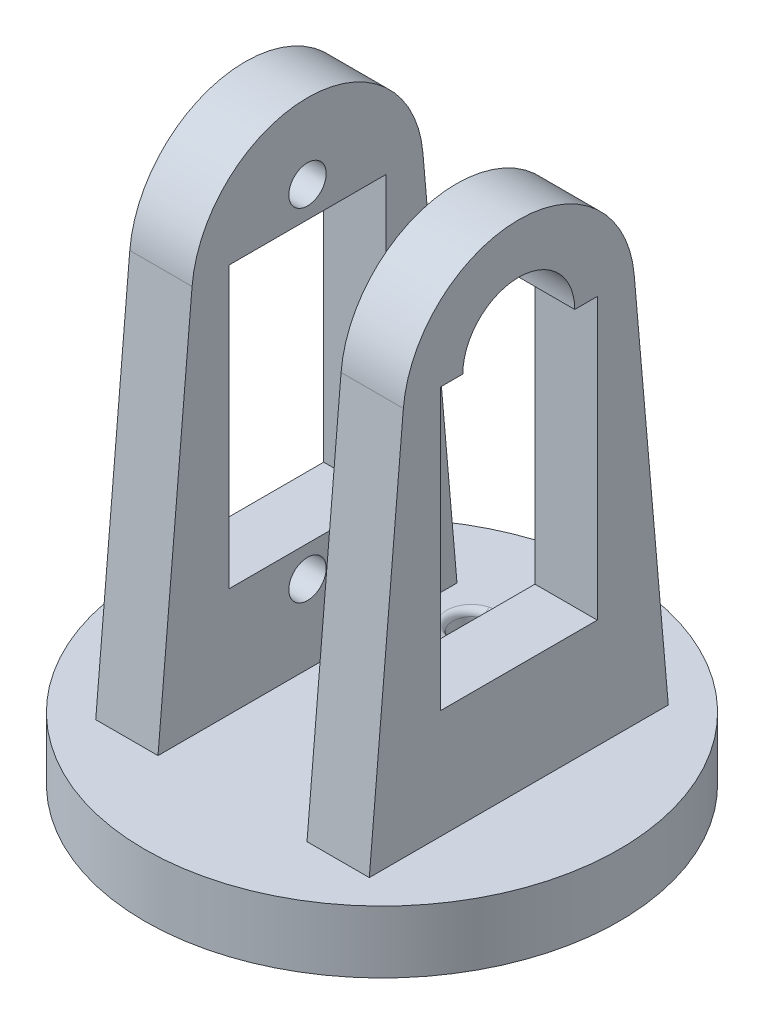
SolidWorks part; units mm, degrees
ref_plane "Front Plane" through (0, 0, 0) normal (0, 0, 1) x (1, 0, 0)
ref_plane "Top Plane" through (0, 0, 0) normal (0, 1, 0) x (1, 0, 0)
ref_plane "Right Plane" through (0, 0, 0) normal (1, 0, 0) x (0, 0, -1)
sketch "Sketch1" plane through (0, 0, 0) normal (0, 1, 0) x (1, 0, 0)
  circle A0 centre (0, 0) radius 2.75
  circle A1 centre (0, 0) radius 19.05
  dimension "D1" = 5.5
  dimension "D2" = 38.1
extrude "Boss-Extrude1" add sketch "Sketch1" along normal blind 5
sketch "Sketch4" plane through (0, 0, 0) normal (0, 1, 0) x (1, 0, 0)
  line L1 (0, 4.6419) -> (-4.02, 2.3209)
  line L2 (-4.02, 2.3209) -> (-4.02, -2.3209)
  line L3 (-4.02, -2.3209) -> (0, -4.6419)
  line L4 (0, -4.6419) -> (4.02, -2.3209)
  line L5 (4.02, -2.3209) -> (4.02, 2.3209)
  line L6 (4.02, 2.3209) -> (0, 4.6419)
  circle A0 centre (0, 0) radius 4.02 construction
  dimension "D1" = 8.04
extrude "Cut-Extrude1" cut sketch "Sketch4" along normal blind 4.1
ref_plane "Plane1" through (-10.98, 0, 0) normal (-1, 0, 0) x (0, 0, 1)
sketch "Sketch5" plane through (-10.98, 0, 0) normal (-1, 0, 0) x (0, 0, 1)
  line L0 (-12, 5) -> (12, 5)
  line L1 (-6.3, 13.75) -> (6.3, 13.75)
  line L2 (-6.3, 13.75) -> (-6.3, 36.25)
  line L3 (-6.3, 36.25) -> (6.3, 36.25)
  line L4 (6.3, 13.75) -> (6.3, 36.25)
  line L5 (-6.3, 13.75) -> (6.3, 36.25) construction
  line L6 (-6.3, 36.25) -> (6.3, 13.75) construction
  line L7 (19.05, 5) -> (-19.05, 5) construction
  line L8 (0, 0) -> (0, -50000) construction
  line L9 (-12, 5) -> (-9.266, 36.25)
  line L10 (12, 5) -> (9.266, 36.25)
  arc A0 (-9.266, 36.25) -> (9.266, 36.25) centre (0, 35.4393) cw
  point P0 (0, 25)
  dimension "D4" = 85
  dimension "D1" = 22.5
  dimension "D2" = 12.6
  dimension "D3" = 25
  dimension "D5" = 12
extrude "Boss-Extrude2" add sketch "Sketch5" against normal blind 5
mirror "Mirror1" about plane through (0, 0, 0) normal (1, 0, 0) of "Boss-Extrude2"
sketch "Sketch6" plane through (-10.98, 0, 0) normal (-1, 0, 0) x (0, 0, 1)
  arc A0 (-0.6692, 40.0585) -> (0.6008, 40.0904) centre (0, 38.716) ccw construction
  arc A1 (0.6008, 9.9096) -> (-0.6692, 9.9415) centre (0, 11.284) ccw construction
  arc A2 (-0.6692, 40.0585) -> (0.6008, 40.0904) centre (0, 38.716) ccw
  arc A3 (0.6008, 9.9096) -> (-0.6692, 9.9415) centre (0, 11.284) ccw
  arc A4 (-0.6692, 9.9415) -> (0.6008, 9.9096) centre (0, 11.284) ccw
  arc A5 (-0.6692, 40.0585) -> (0.6008, 40.0904) centre (0, 38.716) cw
extrude "Cut-Extrude2" cut sketch "Sketch6" against normal up to surface (5 mm away) up to face at (-5.98, 25, 0)
sketch "Sketch7" plane through (5.98, 0, 0) normal (-1, 0, 0) x (0, 0, 1)
  line L0 (6.3, 36.25) -> (-6.3, 36.25) construction
  line L1 (-4.4907, 36.25) -> (4.4907, 36.25)
  arc A0 (4.4907, 36.25) -> (-4.4907, 36.25) centre (0, 36.25) ccw
  arc A4 (9.266, 36.25) -> (-9.266, 36.25) centre (0, 35.4393) ccw construction
  arc A5 (9.266, 36.25) -> (-9.266, 36.25) centre (0, 35.4393) ccw construction
  circle A6 centre (0, 36.25) radius 8.4907 construction
  dimension "D1" = 4
extrude "Cut-Extrude3" cut sketch "Sketch7" against normal up to surface (5 mm away) up to face at (10.98, 22.7477, 0)
sketch "Sketch10" plane through (0, 5, 0) normal (0, 1, 0) x (1, 0, 0)
  circle A0 centre (0, 0) radius 10 construction
  arc A1 (2.5, 9.6825) -> (-2.5, 9.6825) centre (0, 0) ccw construction
  arc A2 (2.875, 11.1348) -> (-2.875, 11.1348) centre (0, 0) ccw
  arc A3 (2.125, 8.2301) -> (-2.125, 8.2301) centre (0, 0) ccw
  arc A4 (2.125, 8.2301) -> (2.875, 11.1348) centre (2.5, 9.6825) ccw
  arc A5 (-2.875, 11.1348) -> (-2.125, 8.2301) centre (-2.5, 9.6825) ccw
  point P5 (0, 10)
  point P10 (0, 0)
  point P11 (0, 0)
  point P12 (0, 0)
  point P13 (0, 10)
  dimension "D1" = 20
  dimension "D2" = 5
  dimension "D3" = 3
extrude "Cut-Extrude6" cut sketch "Sketch10" against normal up to surface (5 mm away) up to face at (0, 0, 19.05)
fillet "Fillet1" radius 0.5 8 edges at (-3.9524, 5, -9.3075) (0, 5, -11.5) (3.9524, 5, -9.3075) (3.9524, 0, -9.3075) (0, 0, -11.5) (-3.9524, 0, -9.3075) (0, 5, -8.5) (0, 0, -8.5)
